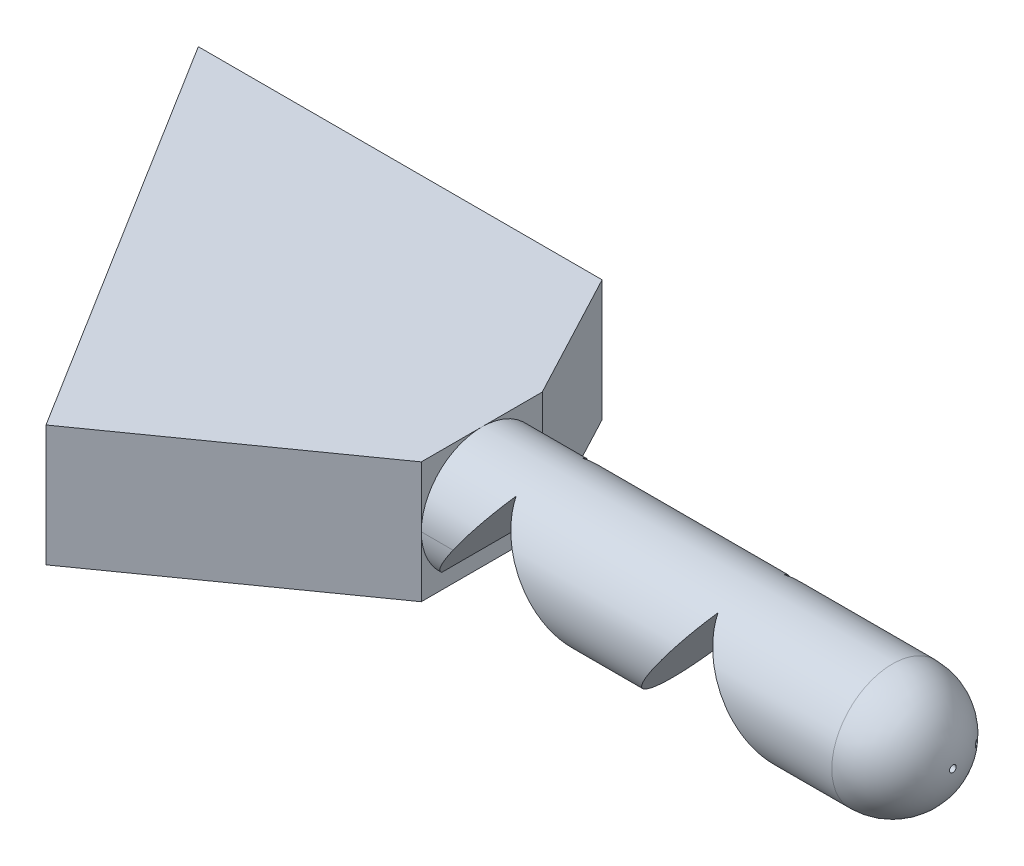
SolidWorks part; units mm, degrees
ref_plane "Front Plane" through (0, 0, 0) normal (0, 0, 1) x (1, 0, 0)
ref_plane "Top Plane" through (0, 0, 0) normal (0, 1, 0) x (1, 0, 0)
ref_plane "Right Plane" through (0, 0, 0) normal (1, 0, 0) x (0, 0, -1)
sketch "Sketch1" plane through (0, 0, 0) normal (0, 0, 1) x (1, 0, 0)
  line L1 (0, 0) -> (70, 0)
  line L2 (0, 0) -> (0, 9)
  line L3 (0, 9) -> (70, 9)
  line L4 (70, 0) -> (70, 9)
  dimension "D1" = 70
  dimension "D2" = 9
revolve "Revolve1" add sketch "Sketch1" angle 360 about L3
fillet "Fillet1" radius 9 1 edges at (70, 9, 9)
sketch "Sketch2" plane through (0, 0, 0) normal (0, 0, 1) x (1, 0, 0)
  line L0 (0, 0) -> (70, 0)
  line L1 (40, 0) -> (40, 16.5429)
  line L2 (40, 16.5429) -> (51.5835, 0)
  line L3 (40, 16.5429) -> (28.4165, 0)
  line L4 (10, 0) -> (10, 16.5429)
  line L5 (10, 16.5429) -> (21.5835, 0)
  line L6 (28.4165, 0) -> (51.5835, 0)
  line L7 (10, 16.5429) -> (-1.5835, 0)
  line L8 (-1.5835, 0) -> (21.5835, 0)
  dimension "D1" = 30
  dimension "D2" = 70
  dimension "D3" = 35
  dimension "D4" = 2
extrude "Cut-Extrude1" cut sketch "Sketch2" against normal mid plane 30 contours L1 L3 L0 | L2 L1 L0 | L0 | L5 L8 L7 region at (36.1388, 5.5143, 0) region at (13.8612, 5.5143, 0) region at (43.8612, 5.5143, 0)
ref_plane "Plane1" through (0, 0, 0) normal (-1, 0, 0) x (0, 0, 1)
sketch "Sketch4" plane through (0, 0, 0) normal (-1, 0, 0) x (0, 0, 1)
  line L0 (-5, 9) -> (5, 9) construction
  circle A0 centre (0, 9) radius 0.2
  circle A2 centre (0, 9) radius 0.2
  circle A3 centre (-5, 9) radius 0.2
  circle A4 centre (5, 9) radius 0.2 [skipped]
  point P5 (0, 9)
  dimension "D1" = 0.4
  dimension "D2" = 10
  dimension "D3" = 2
  dimension "D4" = 2
extrude "Cut-Extrude2" cut sketch "Sketch4" against normal through all contours A3 | L0 A2 | A0 L0 region at (0, 9.0849, 0) region at (0, 8.9151, 0) region at (0, 9, -5.1943)
ref_plane "Plane2" through (69.9978, 0, 0) normal (1, 0, 0) x (0, 0, -1)
sketch "Sketch5" plane through (69.9978, 0, 0) normal (1, 0, 0) x (0, 0, -1)
  circle A1 centre (0, 9) radius 0.5
  circle A2 centre (5, 9) radius 0.5
extrude "Cut-Extrude3" cut sketch "Sketch5" against normal blind 5 draft 3
sketch "Sketch6" plane through (0, 0, 0) normal (0, 1, 0) x (1, 0, 0)
  line L0 (0, -9) -> (-32.632, -32.1334)
  line L1 (0, 8.6562) -> (0, -8.6562) construction
  line L2 (0, -9) -> (4.7184, -9) construction
  line L3 (0, 8.9747) -> (-10, 27.8666)
  line L4 (-10, 27.8666) -> (-32.632, -32.1334)
  line L5 (-10, 27.8666) -> (-70, 27.8666)
  line L6 (-70, 27.8666) -> (-32.632, -32.1334)
  line L7 (0, 8.9747) -> (0, -9)
  point P9 (-64.2702, 17.2564)
  dimension "D1" = 34
  dimension "D2" = 10
  dimension "D3" = 60
  dimension "D4" = 40
  dimension "D5" = 60
  dimension "D6" = 60
extrude "Boss-Extrude1" add sketch "Sketch6" along normal blind 18 contours L7 L3 L4 L0 | L5 L6 L4 region at (-12.9994, 0, 2.8963) region at (-37.544, 0, -7.8666)
